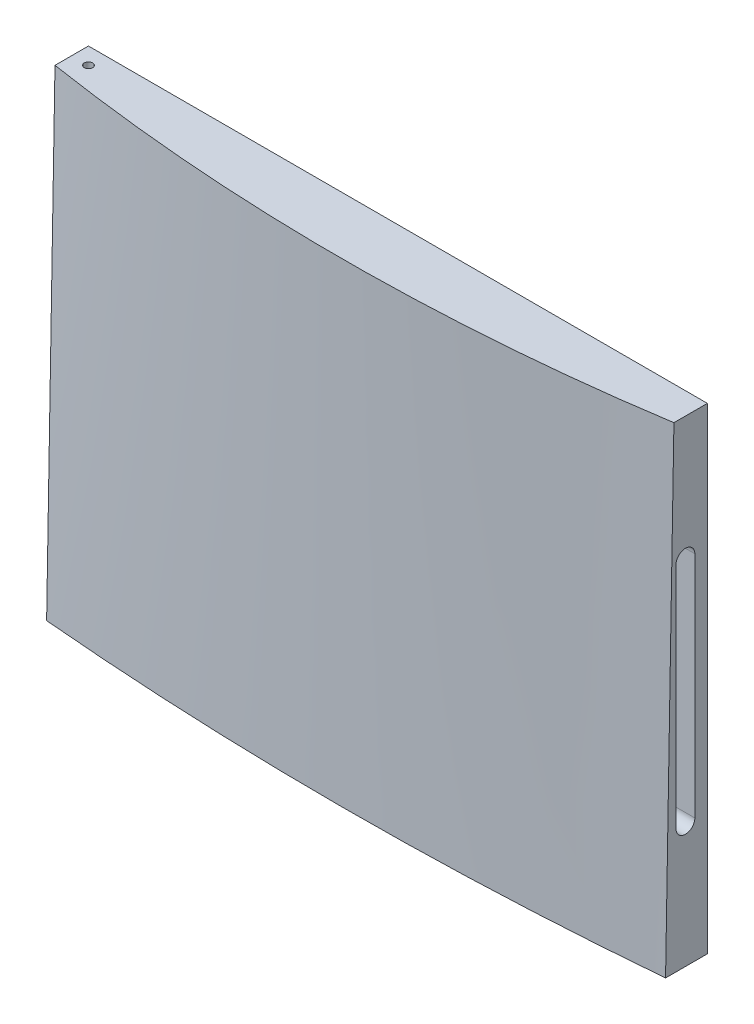
SolidWorks part; units mm, degrees
material "Aço cromo inoxidável"
ref_plane "Plano frontal" through (0, 0, 0) normal (0, 0, 1) x (1, 0, 0)
ref_plane "Plano superior" through (0, 0, 0) normal (0, 1, 0) x (1, 0, 0)
ref_plane "Plano direito" through (0, 0, 0) normal (1, 0, 0) x (0, 0, -1)
sketch "Esboço1" plane through (0, 0, 0) normal (0, 1, 0) x (1, 0, 0)
  line L0 (-370, 0) -> (370, 0)
  line L1 (-370, 0) -> (-370, -50)
  line L2 (370, 0) -> (370, -50)
  arc A0 (-370, -50) -> (370, -50) centre (0, 4133.6706) ccw
  point P3 (0, 0)
  dimension "D1" = 740
  dimension "D3" = 4200
  dimension "D2" = 50
ref_plane "Plano1" through (0, 570, 0) normal (0, 1, 0) x (1, 0, 0)
sketch "Esboço2" plane through (0, 570, 0) normal (0, 1, 0) x (1, 0, 0)
  line L0 (370, 0) -> (370, -50) construction
  line L1 (-370, 0) -> (370, 0)
  line L2 (-370, 0) -> (-370, -40)
  line L4 (370, 0) -> (370, -40)
  arc A0 (-370, -40) -> (370, -40) centre (0, 2331.3077) ccw
  dimension "D2" = 2400
  dimension "D1" = 40
  dimension "D3" = 740
loft "Loft1" add profiles "Esboço2", "Esboço1"
sketch "Esboço5" plane through (0, 0, 0) normal (0, -1, 0) x (1, 0, 0)
  line L0 (-370, 0) -> (-370, 50) construction
  line L1 (370, 0) -> (-370, 0) construction
  circle A0 centre (-350, 20) radius 5
  dimension "D3" = 10
  dimension "D1" = 20
  dimension "D2" = 20
extrude "Corte-extrusão3" cut sketch "Esboço5" against normal up to next contours A0
sketch "Esboço6" plane through (0, 0, 0) normal (0, -1, 0) x (1, 0, 0)
  line L1 (-370, 0) -> (-320.8568, 0)
  line L2 (-370, 0) -> (-370, 25.4419)
  line L3 (-370, 25.4419) -> (-335.8568, 25.4419)
  line L4 (-320.8568, 0) -> (-320.8568, 10.4419)
  arc A0 (-335.8568, 25.4419) -> (-320.8568, 10.4419) centre (-335.8568, 10.4419) cw
  dimension "D1" = 15
  dimension "D2" = 34.1432
extrude "Corte-extrusão4" cut sketch "Esboço6" against normal blind 10 contours L3 A0 L4 L1 L2
sketch "Esboço8" plane through (0, 0, 0) normal (0, 0, -1) x (-1, 0, 0)
  line L1 (335, 35) -> (-345, 35)
  line L2 (335, 35) -> (335, 545)
  line L3 (335, 545) -> (-345, 545)
  line L4 (-345, 35) -> (-345, 545)
  line L5 (-370, 570) -> (-370, 0) construction
  line L6 (370, 570) -> (370, 10) construction
  line L7 (37.79, 570) -> (-37.79, 570) construction
  line L8 (370, 10) -> (320.8568, 10) construction
  dimension "D1" = 25
  dimension "D2" = 25
  dimension "D3" = 35
  dimension "D4" = 25
extrude "Ressalto-extrusão1" add sketch "Esboço8" along normal blind 20
fillet "Filete1" radius 10 9 edges at (5, 545, 0) (345, 545, -10) (345, 290, -20) (345, 290, 0) (-335, 290, -20) (-335, 545, -10) (-335, 290, 0) (5, 35, -20) (5, 35, 0)
sketch "Esboço11" plane through (370, 0, 0) normal (1, 0, 0) x (0, 0, -1)
  line L0 (-26.25, 0) -> (-26.25, 570) construction
  line L1 (0, 570) -> (0, 0) construction
  line L3 (-37.5, 148.2) -> (-37.5, 421.8)
  line L5 (-15, 148.2) -> (-15, 421.8)
  line L7 (37.79, 570) -> (-37.79, 570) construction
  arc A0 (-15, 148.2) -> (-37.5, 148.2) centre (-26.25, 148.2) cw
  arc A1 (-15, 421.8) -> (-37.5, 421.8) centre (-26.25, 421.8) ccw
  point P16 (-26.25, 285)
  point P17 (-37.5, 285)
  dimension "D1" = 273.6
  dimension "D2" = 15
  dimension "D4" = 22.5
extrude "Corte-extrusão5" cut sketch "Esboço11" against normal blind 35
fillet "Filete17" radius 10 4 edges at (335, 433.05, 26.25) (335, 285, 15) (335, 136.95, 26.25) (335, 285, 37.5)
